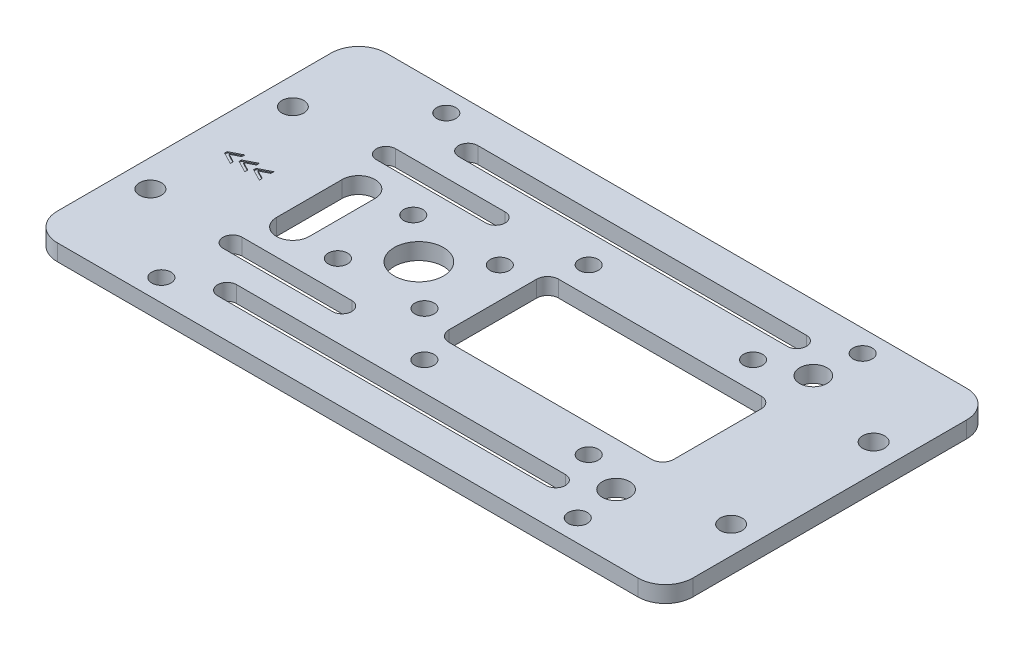
SolidWorks part; units mm, degrees
ref_plane "Front Plane" through (0, 0, 0) normal (0, 0, 1) x (1, 0, 0)
ref_plane "Top Plane" through (0, 0, 0) normal (0, 1, 0) x (1, 0, 0)
ref_plane "Right Plane" through (0, 0, 0) normal (1, 0, 0) x (0, 0, -1)
sketch "Sketch1" plane through (0, 0, 0) normal (0, 1, 0) x (1, 0, 0)
  line L0 (-58, 0) -> (58, 0) construction
  line L1 (-58, 30) -> (58, 30)
  line L2 (-58, 30) -> (-58, -30)
  line L3 (-58, -30) -> (58, -30)
  line L4 (58, 30) -> (58, -30)
  line L5 (-58, 30) -> (58, -30) construction
  line L6 (-58, -30) -> (58, 30) construction
  line L7 (0, 30) -> (0, -30) construction
  circle A0 centre (53, 13) radius 2
  circle A1 centre (53, -13) radius 2
  circle A2 centre (-53, -13) radius 2
  circle A3 centre (-53, 13) radius 2
  point P0 (0, 0)
  dimension "D4" = 4
  dimension "D1" = 60
  dimension "D2" = 116
  dimension "D3" = 13
  dimension "D5" = 53
extrude "Boss-Extrude1" add sketch "Sketch1" along normal blind 3
sketch "Sketch2" plane through (0, 3, 0) normal (0, 1, 0) x (1, 0, 0)
  line L0 (-58, 0) -> (58, 0) construction
  line L1 (-58, 30) -> (-58, -30) construction
  line L2 (58, -30) -> (58, 30) construction
  line L3 (0, 30) -> (0, -30) construction
  line L4 (58, 30) -> (-58, 30) construction
  line L5 (-58, -30) -> (58, -30) construction
  circle A0 centre (38, 26) radius 1.75
  circle A1 centre (38, -26) radius 1.75
  circle A2 centre (-38, -26) radius 1.75
  circle A3 centre (-38, 26) radius 1.75
  dimension "D1" = 3.5
  dimension "D2" = 26
  dimension "D3" = 38
extrude "Odroid-holes" cut sketch "Sketch2" against normal through all
sketch "Sketch3" plane through (0, 3, 0) normal (0, 1, 0) x (1, 0, 0)
  text T0 "<b><<<</b>"
extrude "Cut-Extrude2" cut sketch "Sketch3" against normal blind 0.2
sketch "Sketch4" plane through (0, 3, 0) normal (0, 1, 0) x (1, 0, 0)
  line L0 (58, 0) -> (-58, 0) construction
  line L1 (58, -30) -> (58, 30) construction
  line L2 (-58, 30) -> (-58, -30) construction
  line L3 (14, 30) -> (14, -30) construction
  line L4 (58, 30) -> (-58, 30) construction
  line L5 (-58, -30) -> (58, -30) construction
  line L6 (0, 30) -> (0, -30) construction
  circle A0 centre (-1, 15) radius 1.75
  circle A1 centre (29, 15) radius 1.75
  circle A2 centre (29, -15) radius 1.75
  circle A3 centre (-1, -15) radius 1.75
  dimension "D1" = 3.5
  dimension "D2" = 15
  dimension "D3" = 15
  dimension "D4" = 14
extrude "Pixhawk-PM" cut sketch "Sketch4" against normal through all
sketch "Sketch5" plane through (0, 3, 0) normal (0, 1, 0) x (1, 0, 0)
  line L0 (0, 30) -> (0, -30) construction
  line L1 (58, 30) -> (-58, 30) construction
  line L2 (-58, -30) -> (58, -30) construction
  line L3 (-17, 30) -> (-17, -30) construction
  line L4 (-58, 0) -> (58, 0) construction
  line L5 (-58, 30) -> (-58, -30) construction
  line L6 (58, -30) -> (58, 30) construction
  circle A0 centre (-9.1, 6.875) radius 1.75
  circle A1 centre (-24.9, 6.875) radius 1.75
  circle A2 centre (-24.9, -6.875) radius 1.75
  circle A3 centre (-9.1, -6.875) radius 1.75
  dimension "D1" = 3.5
  dimension "D2" = 6.875
  dimension "D3" = 7.9
  dimension "D4" = 17
extrude "BuckConverter-5A" cut sketch "Sketch5" against normal through all
sketch "Sketch6" plane through (0, 3, 0) normal (0, 1, 0) x (1, 0, 0)
  line L0 (-58, 0) -> (58, 0) construction
  line L1 (-58, 30) -> (-58, -30) construction
  line L2 (58, -30) -> (58, 30) construction
  line L3 (0, 30) -> (0, -30) construction
  line L4 (58, 30) -> (-58, 30) construction
  line L5 (-58, -30) -> (58, -30) construction
  line L6 (-30, 22) -> (30, 22) construction
  line L7 (-30, 23.75) -> (30, 23.75)
  line L8 (-30, 20.25) -> (30, 20.25)
  line L9 (-30, -22) -> (30, -22) construction
  line L10 (-30, -23.75) -> (30, -23.75)
  line L11 (-30, -20.25) -> (30, -20.25)
  line L12 (-37, 14) -> (-17, 14) construction
  line L13 (-37, 15.75) -> (-17, 15.75)
  line L14 (-37, 12.25) -> (-17, 12.25)
  line L15 (-37, -14) -> (-17, -14) construction
  line L16 (-37, -15.75) -> (-17, -15.75)
  line L17 (-37, -12.25) -> (-17, -12.25)
  line L78 (-24.9, 6.875) -> (-9.1, 6.875) construction
  line L79 (-1.5, 10) -> (35.5, 10)
  line L80 (-3.5, 8) -> (-3.5, -8)
  line L81 (-1.5, -10) -> (35.5, -10)
  line L82 (37.5, 8) -> (37.5, -8)
  line L83 (-3.5, 10) -> (37.5, -10) construction
  line L84 (-3.5, -10) -> (37.5, 10) construction
  line L85 (-9.1, 6.875) -> (-9.1, -6.875) construction
  line L86 (-9.1, -6.875) -> (-24.9, -6.875) construction
  line L87 (-24.9, -6.875) -> (-24.9, 6.875) construction
  line L88 (-17, 6.875) -> (-17, -6.875) construction
  line L89 (-34, 30) -> (-34, -30) construction
  line L90 (-34, 6) -> (-34, -6) construction
  line L91 (-31, 6) -> (-31, -6)
  line L92 (-37, 6) -> (-37, -6)
  arc A0 (-30, 23.75) -> (-30, 20.25) centre (-30, 22) ccw
  arc A1 (30, 20.25) -> (30, 23.75) centre (30, 22) ccw
  arc A2 (-30, -23.75) -> (-30, -20.25) centre (-30, -22) cw
  arc A3 (30, -20.25) -> (30, -23.75) centre (30, -22) cw
  arc A4 (-37, 15.75) -> (-37, 12.25) centre (-37, 14) ccw
  arc A5 (-17, 12.25) -> (-17, 15.75) centre (-17, 14) ccw
  arc A6 (-37, -15.75) -> (-37, -12.25) centre (-37, -14) cw
  arc A7 (-17, -12.25) -> (-17, -15.75) centre (-17, -14) cw
  arc A48 (35.5, -10) -> (37.5, -8) centre (35.5, -8) ccw
  arc A49 (35.5, 10) -> (37.5, 8) centre (35.5, 8) cw
  arc A50 (-3.5, -8) -> (-1.5, -10) centre (-1.5, -8) ccw
  arc A51 (-1.5, 10) -> (-3.5, 8) centre (-1.5, 8) ccw
  circle A52 centre (37, 18) radius 2.5
  circle A53 centre (37, -18) radius 2.5
  circle A54 centre (-17, 0) radius 4.5
  arc A55 (-31, 6) -> (-37, 6) centre (-34, 6) ccw
  arc A56 (-37, -6) -> (-31, -6) centre (-34, -6) ccw
  point P14 (0, 22)
  point P21 (0, -22)
  point P28 (-27, 14)
  point P36 (-27, -14)
  point P168 (17, 0)
  point P205 (-34, 0)
  dimension "D19" = 2
  dimension "D23" = 9
  dimension "D25" = 3
  dimension "D1" = 22
  dimension "D2" = 3.5
  dimension "D3" = 60
  dimension "D4" = 27
  dimension "D5" = 3.5
  dimension "D6" = 20
  dimension "D7" = 14
  dimension "D16" = 17
  dimension "D17" = 41
  dimension "D18" = 20
  dimension "D21" = 21
  dimension "D24" = 24
  dimension "D26" = 12
extrude "Cut-Extrude5" cut sketch "Sketch6" against normal through all contours L82 L79 L80 L81 | A54 | L7 A1 L8 A0 | L13 A5 L14 A4 | L17 A7 L16 A6 | L11 A3 L10 A2 | A52 | A53 | L91 A56 L92 A55 region at (17, 3, 0) region at (-17, 3, 0)
fillet "Fillet1" radius 5 4 edges at (58, 1.5, -30) (58, 1.5, 30) (-58, 1.5, 30) (-58, 1.5, -30)
